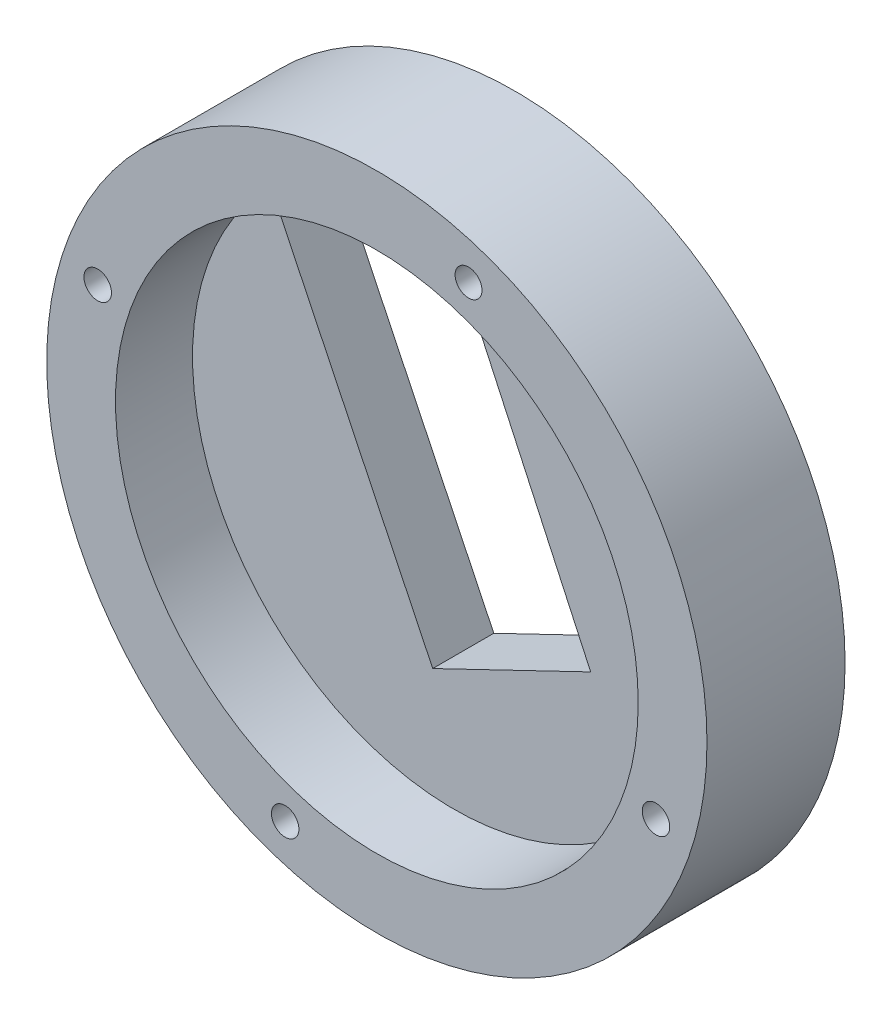
SolidWorks part; units mm, degrees
ref_plane "Front Plane" through (0, 0, 0) normal (0, 0, 1) x (1, 0, 0)
ref_plane "Top Plane" through (0, 0, 0) normal (0, 1, 0) x (1, 0, 0)
ref_plane "Right Plane" through (0, 0, 0) normal (1, 0, 0) x (0, 0, -1)
sketch "Sketch1" plane through (0, 0, 0) normal (0, 0, 1) x (1, 0, 0)
  circle A0 centre (0, 0) radius 60
  dimension "D1" = 120
extrude "Boss-Extrude1" add sketch "Sketch1" along normal blind 25.1
sketch "Sketch2" plane through (0, 0, 25.1) normal (0, 0, 1) x (1, 0, 0)
  circle A0 centre (-16.6647, -50.7331) radius 2.495
  circle A1 centre (-50.7331, 16.6647) radius 2.5
  circle A2 centre (16.6647, 50.7331) radius 2.4444
  circle A3 centre (50.7331, -16.6647) radius 2.5
sketch "Sketch3" plane through (0, 0, 25.1) normal (0, 0, 1) x (1, 0, 0)
  circle A0 centre (0, 0) radius 47.5
  dimension "D1" = 95
extrude "Cut-Extrude2" cut sketch "Sketch3" against normal blind 14
extrude "Cut-Extrude5" cut sketch "Sketch2" against normal through all both and the other way through all
sketch "Sketch6" plane through (0, 0, 0) normal (0, 0, -1) x (-1, 0, 0)
  circle A0 centre (11.9735, 47.2126) radius 3
  circle A1 centre (27.3813, 40.0293) radius 3
  circle A2 centre (-19.7177, -20.7629) radius 3
  circle A3 centre (-4.3099, -27.9462) radius 3
  dimension "D1" = 6
  dimension "D2" = 6
  dimension "D3" = 6
  dimension "D4" = 6
extrude "Cut-Extrude6" cut sketch "Sketch6" against normal blind 6
sketch "Sketch7" plane through (0, 0, 11.1) normal (0, 0, 1) x (1, 0, 0)
  line L0 (-32.7224, 32.7144) -> (-3.8455, -27.2733)
  line L1 (-3.8455, -27.2733) -> (24.8593, -13.4553)
  line L2 (24.8593, -13.4553) -> (-3.0425, 47.0016)
  line L3 (-3.0425, 47.0016) -> (-32.7224, 32.7144)
  circle A0 centre (0, 0) radius 47.1 construction
extrude "Cut-Extrude7" cut sketch "Sketch7" against normal through all both and the other way through all
